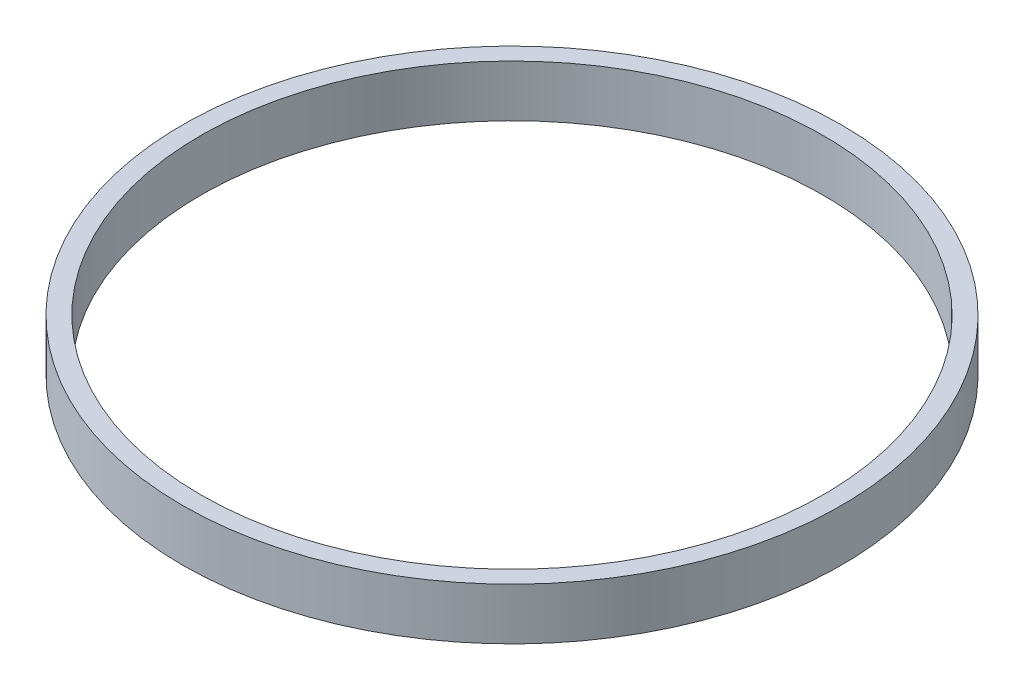
SolidWorks part; units mm, degrees
material "ABS"
ref_plane "Front Plane" through (0, 0, 0) normal (0, 0, 1) x (1, 0, 0)
ref_plane "Top Plane" through (0, 0, 0) normal (0, 1, 0) x (1, 0, 0)
ref_plane "Right Plane" through (0, 0, 0) normal (1, 0, 0) x (0, 0, -1)
sketch "Sketch2" plane through (0, 0, 0) normal (0, 1, 0) x (1, 0, 0)
  circle A0 centre (0, 0) radius 34
  circle A1 centre (0, 0) radius 36
  dimension "D1" = 68
  dimension "D2" = 72
extrude "Boss-Extrude1" add sketch "Sketch2" along normal blind 5.65
equation "\"L1L\"=500"
equation "\"L1Thick\"=6.35"
equation "\"Harm-Drive-Outer\"=74.5"
equation "\"L1-Spacing\"=110"
equation "\"L-Bracket-HoleToWall\"=12.5"
equation "\"L-Bracket-HoleToSide\"=11"
equation "\"Bracket-Hole-D\"=6.8"
